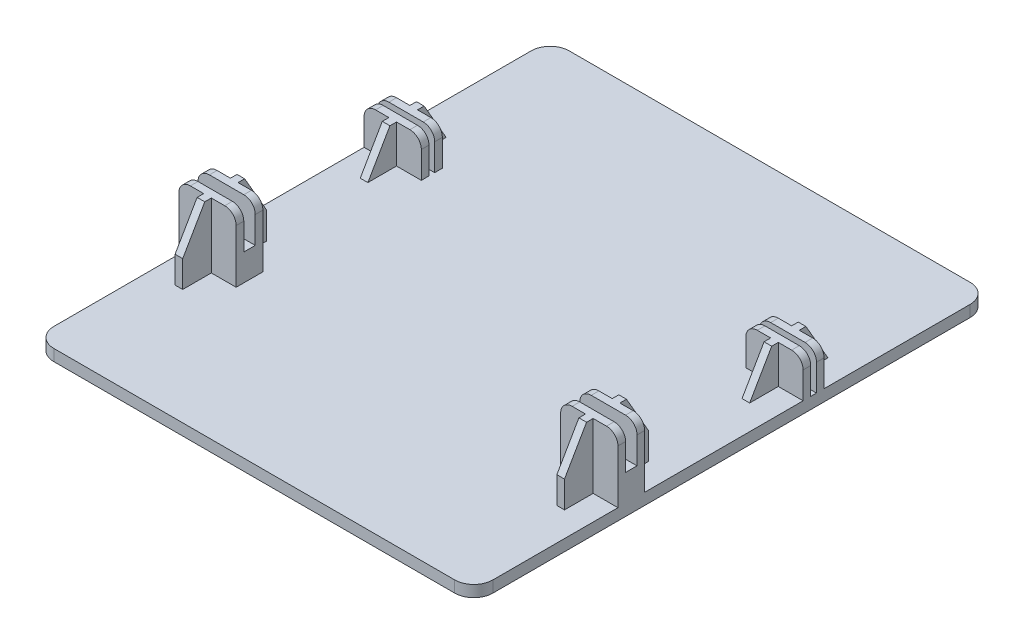
SolidWorks part; units mm, degrees
ref_plane "Plan de face" through (0, 0, 0) normal (0, 0, 1) x (1, 0, 0)
ref_plane "Plan de dessus" through (0, 0, 0) normal (0, 1, 0) x (1, 0, 0)
ref_plane "Plan de droite" through (0, 0, 0) normal (1, 0, 0) x (0, 0, -1)
sketch "Esquisse1" plane through (0, 0, 0) normal (0, 1, 0) x (1, 0, 0)
  line L1 (-57.5, -67.5) -> (57.5, -67.5)
  line L2 (-57.5, -67.5) -> (-57.5, 67.5)
  line L3 (-57.5, 67.5) -> (57.5, 67.5)
  line L4 (57.5, -67.5) -> (57.5, 67.5)
  line L5 (-57.5, -67.5) -> (57.5, 67.5) construction
  line L6 (-57.5, 67.5) -> (57.5, -67.5) construction
  point P0 (60, -28.8934)
  point P6 (0, 0)
  dimension "D1" = 115
  dimension "D2" = 135
extrude "Boss.-Extru.1" add sketch "Esquisse1" along normal blind 3
sketch "Esquisse2" plane through (0, 3, 0) normal (0, 1, 0) x (1, 0, 0)
  line L0 (-57.5, 24.25) -> (-51, 24.25)
  line L1 (-57.5, 67.5) -> (-57.5, -67.5) construction
  line L2 (-42.5, 24.25) -> (-42.5, 22.25)
  line L3 (-42.5, 22.25) -> (-57.5, 22.25)
  line L4 (-57.5, 22.25) -> (-57.5, 24.25)
  line L9 (-49, 24.25) -> (-42.5, 24.25)
  line L10 (-57.5, 21.5) -> (-42.5, 21.5) construction
  line L12 (-51, 24.25) -> (-51, 31.75)
  line L13 (-51, 31.75) -> (-49, 31.75)
  line L14 (-49, 31.75) -> (-49, 24.25)
  line L15 (-42.5, 21.5) -> (-42.5, 22.25) construction
  line L16 (-42.5, 18.75) -> (-42.5, 20.75)
  line L17 (-49, 18.75) -> (-42.5, 18.75)
  line L18 (-49, 11.25) -> (-49, 18.75)
  line L19 (-51, 11.25) -> (-49, 11.25)
  line L20 (-51, 18.75) -> (-51, 11.25)
  line L21 (-57.5, 18.75) -> (-51, 18.75)
  line L22 (-42.5, 20.75) -> (-57.5, 20.75)
  line L23 (-57.5, 20.75) -> (-57.5, 18.75)
  line L24 (57.5, 67.5) -> (-57.5, 67.5) construction
  line L25 (-51, -22.75) -> (-51, -15.25)
  line L26 (-51, -15.25) -> (-49, -15.25)
  line L27 (-49, -15.25) -> (-49, -22.75)
  line L28 (-49, -22.75) -> (-42.5, -22.75)
  line L29 (-42.5, -22.75) -> (-42.5, -24.75)
  line L30 (-42.5, -24.75) -> (-57.5, -24.75)
  line L31 (-57.5, -24.75) -> (-57.5, -22.75)
  line L32 (-57.5, -22.75) -> (-51, -22.75)
  line L33 (-51, 24.25) -> (-51, -22.75) construction
  line L34 (-57.5, -26.25) -> (-42.5, -26.25) construction
  line L35 (-42.5, -26.25) -> (-42.5, -24.75) construction
  line L36 (-57.5, -29.75) -> (-51, -29.75)
  line L37 (-57.5, -27.75) -> (-57.5, -29.75)
  line L38 (-42.5, -27.75) -> (-57.5, -27.75)
  line L39 (-42.5, -29.75) -> (-42.5, -27.75)
  line L40 (-49, -29.75) -> (-42.5, -29.75)
  line L41 (-49, -37.25) -> (-49, -29.75)
  line L42 (-51, -37.25) -> (-49, -37.25)
  line L43 (-51, -29.75) -> (-51, -37.25)
  dimension "D1" = 1.5
  dimension "D2" = 7.5
  dimension "D3" = 2
  dimension "D4" = 15
  dimension "D5" = 46
  dimension "D7" = 47
  dimension "D8" = 3
  dimension "D6" = 2
extrude "Boss.-Extru.2" add sketch "Esquisse2" along normal blind 10
sketch "Esquisse4" plane through (0, 13, 0) normal (0, 1, 0) x (1, 0, 0)
  line L0 (-57.5, -27.75) -> (-57.5, -29.75) construction
  line L1 (-57.5, -29.75) -> (-51, -29.75) construction
  line L2 (-51, -29.75) -> (-51, -37.25) construction
  line L3 (-51, -37.25) -> (-49, -37.25) construction
  line L4 (-49, -37.25) -> (-49, -29.75) construction
  line L5 (-49, -29.75) -> (-42.5, -29.75) construction
  line L6 (-42.5, -29.75) -> (-42.5, -27.75) construction
  line L7 (-42.5, -27.75) -> (-57.5, -27.75) construction
  line L8 (-51, -22.75) -> (-57.5, -22.75) construction
  line L9 (-57.5, -22.75) -> (-57.5, -24.75) construction
  line L10 (-57.5, -24.75) -> (-42.5, -24.75) construction
  line L11 (-42.5, -24.75) -> (-42.5, -22.75) construction
  line L12 (-42.5, -22.75) -> (-49, -22.75) construction
  line L13 (-49, -22.75) -> (-49, -15.25) construction
  line L14 (-49, -15.25) -> (-51, -15.25) construction
  line L15 (-51, -15.25) -> (-51, -22.75) construction
  line L16 (-57.5, -27.75) -> (-57.5, -29.75)
  line L17 (-57.5, -29.75) -> (-51, -29.75)
  line L18 (-51, -29.75) -> (-51, -37.25)
  line L19 (-51, -37.25) -> (-49, -37.25)
  line L20 (-49, -37.25) -> (-49, -29.75)
  line L21 (-49, -29.75) -> (-42.5, -29.75)
  line L22 (-42.5, -29.75) -> (-42.5, -27.75)
  line L23 (-42.5, -27.75) -> (-57.5, -27.75)
  line L24 (-51, -22.75) -> (-57.5, -22.75)
  line L25 (-57.5, -22.75) -> (-57.5, -24.75)
  line L26 (-57.5, -24.75) -> (-42.5, -24.75)
  line L27 (-42.5, -24.75) -> (-42.5, -22.75)
  line L28 (-42.5, -22.75) -> (-49, -22.75)
  line L29 (-49, -22.75) -> (-49, -15.25)
  line L30 (-49, -15.25) -> (-51, -15.25)
  line L31 (-51, -15.25) -> (-51, -22.75)
extrude "Boss.-Extru.3" add sketch "Esquisse4" along normal blind 7
sketch "Esquisse5" plane through (0, 3, 0) normal (0, 1, 0) x (1, 0, 0)
  line L0 (-57.5, -24.75) -> (-42.5, -24.75)
  line L1 (-42.5, -24.75) -> (-42.5, -27.75)
  line L2 (-42.5, -27.75) -> (-57.5, -27.75)
  line L3 (-57.5, -27.75) -> (-57.5, -24.75)
extrude "Boss.-Extru.4" add sketch "Esquisse5" along normal blind 7
chamfer "Chanfrein1" distance 10 angle 30 4 edges at (-50, 13, -31.75) (-50, 13, -11.25) (-50, 20, 37.25) (-50, 20, 15.25) first distance on face at (-50, 8, -31.75) first distance on face at (-50, 8, -11.25) first distance on face at (-50, 11.5, 37.25) first distance on face at (-50, 11.5, 15.25)
fillet "Congé1" radius 3 8 edges at (-57.5, 13, -19.75) (-57.5, 13, -23.25) (-42.5, 13, -23.25) (-42.5, 13, -19.75) (-57.5, 20, 23.75) (-57.5, 20, 28.75) (-42.5, 20, 23.75) (-42.5, 20, 28.75)
mirror "Symétrie1" about plane through (0, 0, 0) normal (1, 0, 0) of "Congé1", "Chanfrein1", "Boss.-Extru.4", "Boss.-Extru.3", "Boss.-Extru.2"
fillet "Congé2" radius 5 4 edges at (-57.5, 1.5, -67.5) (57.5, 1.5, -67.5) (57.5, 1.5, 67.5) (-57.5, 1.5, 67.5)
